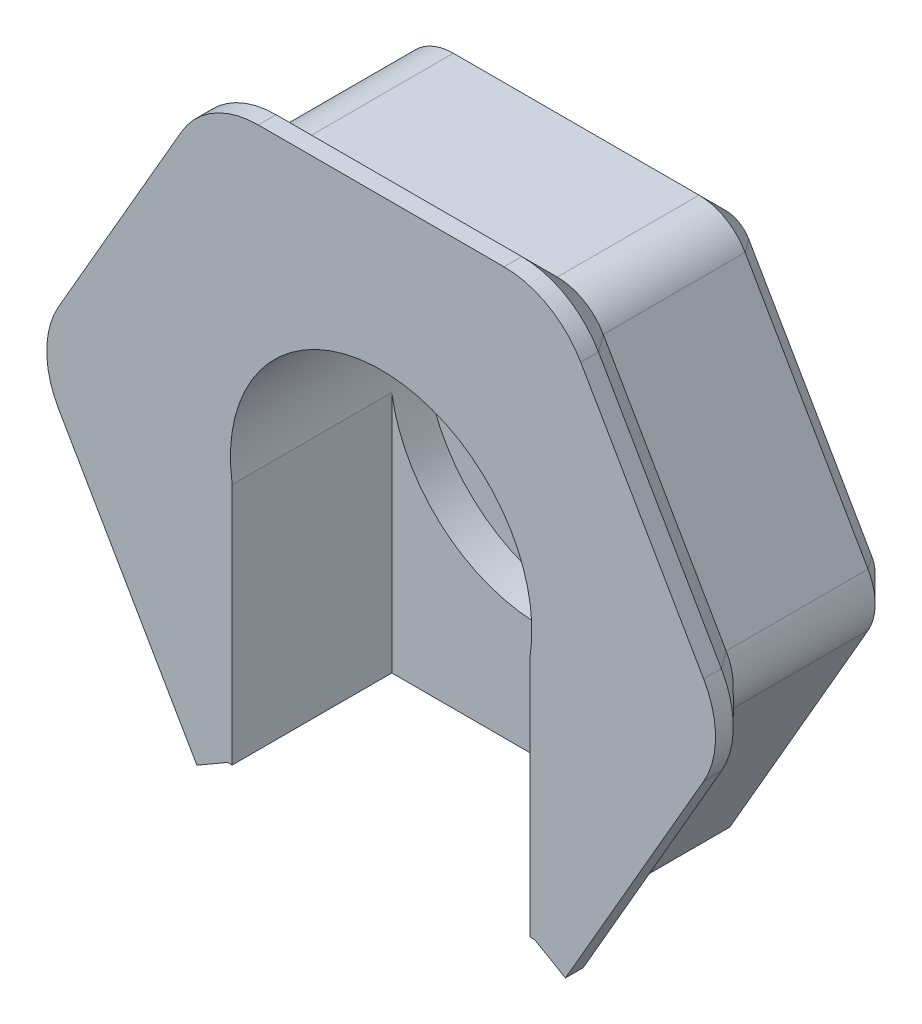
SolidWorks part; units mm, degrees
ref_plane "Front Plane" through (0, 0, 0) normal (0, 0, 1) x (1, 0, 0)
ref_plane "Top Plane" through (0, 0, 0) normal (0, 1, 0) x (1, 0, 0)
ref_plane "Right Plane" through (0, 0, 0) normal (1, 0, 0) x (0, 0, -1)
sketch "Sketch1" plane through (0, 0, 0) normal (0, 0, 1) x (1, 0, 0)
  line L1 (8.6603, 15) -> (-8.6603, 15)
  line L2 (-8.6603, 15) -> (-17.3205, 0)
  line L3 (-17.3205, 0) -> (-8.6603, -15)
  line L4 (-8.6603, -15) -> (8.6603, -15)
  line L5 (8.6603, -15) -> (17.3205, 0)
  line L6 (17.3205, 0) -> (8.6603, 15)
  circle A0 centre (0, 0) radius 15
  circle A1 centre (0, 0) radius 8.5
  circle A2 centre (0, 0) radius 15 construction
  dimension "D1" = 30
  dimension "D2" = 17
extrude "Boss-Extrude1" add sketch "Sketch1" along normal blind 1.5 contours A1 region at (0, 0, 0)
extrude "Boss-Extrude2" add sketch "Sketch1<4>" along normal offset from surface (12.5 mm away) 11 contours A0 A1 | A0 L6 L1 | A0 L1 L2 | A0 L2 L3 | A0 L5 L6 | A0 L4 L5 | A0 L3 L4 region at (7.7517, 13.4264, 0) region at (-7.7517, 13.4264, 0) region at (7.2879, 12.623, 0) region at (15.5034, 0, 0) region at (-15.5034, 0, 0) region at (-7.7517, -13.4264, 0) region at (7.7517, -13.4264, 0) up to face at (8.5, 0, 1.5) offset beyond the face yes
sketch "Sketch1<4>" plane through (0, 0, 0) normal (0, 0, 1) x (1, 0, 0) same geometry as "Sketch1"
sketch "Sketch2" plane through (0, 0, 1.5) normal (0, 0, 1) x (1, 0, 0)
  line L1 (-8.4, 0) -> (8.4, 0)
  line L2 (-8.4, 0) -> (-8.4, -15)
  line L3 (-8.4, -15) -> (8.4, -15)
  line L4 (8.4, 0) -> (8.4, -15)
  point P5 (0, 0)
  dimension "D1" = 16.8
  dimension "D2" = 15
extrude "Cut-Extrude1" cut sketch "Sketch2" along normal through all from offset 2
fillet "Fillet1" radius 3 4 edges at (-17.3205, 0, 6.25) (-8.6603, 15, 6.25) (8.6603, 15, 6.25) (17.3205, 0, 6.25)
sketch "Sketch3" plane through (0, 0, 1.5) normal (0, 0, 1) x (1, 0, 0)
  circle A0 centre (0, 0) radius 3.15
  dimension "D1" = 6.3
extrude "Cut-Extrude2" cut sketch "Sketch3" against normal through all
fillet "Fillet3" radius 1.5 10 edges at (12.5574, -8.25, 0) (16.8564, 0, 0) (12.9904, 7.5, 0) (8.4282, 14.5981, 0) (0, 15, 0) (-8.4282, 14.5981, 0) (-12.9904, 7.5, 0) (-16.8564, 0, 0) (0, -15, 0) (-12.5574, -8.25, 0) profile chamfer
sketch "Sketch5" plane through (0, 0, 12.5) normal (0, 0, 1) x (1, 0, 0)
  line L5 (-10.3923, -16) -> (-8.6603, -15)
  line L6 (10.3923, -16) -> (8.6603, -15)
  line L7 (8.6603, -15) -> (16.4545, -1.5) construction
  line L8 (16.4545, 1.5) -> (9.5263, 13.5) construction
  line L9 (6.9282, 15) -> (-6.9282, 15) construction
  line L10 (-18.1865, -2.5) -> (-10.3923, -16)
  line L11 (-11.2583, 14.5) -> (-18.1865, 2.5)
  line L12 (6.9282, 17) -> (-6.9282, 17)
  line L13 (18.1865, 2.5) -> (11.2583, 14.5)
  line L14 (10.3923, -16) -> (18.1865, -2.5)
  line L15 (-18.1865, -2.5) -> (-10.3923, -16)
  line L16 (-11.2583, 14.5) -> (-18.1865, 2.5)
  line L17 (6.9282, 17) -> (-6.9282, 17)
  line L18 (18.1865, 2.5) -> (11.2583, 14.5)
  line L19 (10.3923, -16) -> (18.1865, -2.5)
  line L20 (-9.5263, 13.5) -> (-16.4545, 1.5) construction
  line L21 (-16.4545, -1.5) -> (-8.6603, -15) construction
  line L22 (8.6603, -15) -> (16.4545, -1.5)
  line L23 (16.4545, 1.5) -> (9.5263, 13.5)
  line L24 (6.9282, 15) -> (-6.9282, 15)
  line L25 (-9.5263, 13.5) -> (-16.4545, 1.5)
  line L26 (-16.4545, -1.5) -> (-8.6603, -15)
  arc A4 (16.4545, -1.5) -> (16.4545, 1.5) centre (13.8564, 0) ccw construction
  arc A5 (9.5263, 13.5) -> (6.9282, 15) centre (6.9282, 12) ccw construction
  arc A6 (-6.9282, 15) -> (-9.5263, 13.5) centre (-6.9282, 12) ccw construction
  arc A7 (-16.4545, 1.5) -> (-16.4545, -1.5) centre (-13.8564, 0) ccw construction
  arc A8 (-18.1865, 2.5) -> (-18.1865, -2.5) centre (-13.8564, 0) ccw
  arc A9 (-6.9282, 17) -> (-11.2583, 14.5) centre (-6.9282, 12) ccw
  arc A10 (11.2583, 14.5) -> (6.9282, 17) centre (6.9282, 12) ccw
  arc A11 (18.1865, -2.5) -> (18.1865, 2.5) centre (13.8564, 0) ccw
  arc A12 (-18.1865, 2.5) -> (-18.1865, -2.5) centre (-13.8564, 0) ccw
  arc A13 (-6.9282, 17) -> (-11.2583, 14.5) centre (-6.9282, 12) ccw
  arc A14 (11.2583, 14.5) -> (6.9282, 17) centre (6.9282, 12) ccw
  arc A15 (18.1865, -2.5) -> (18.1865, 2.5) centre (13.8564, 0) ccw
  arc A16 (16.4545, -1.5) -> (16.4545, 1.5) centre (13.8564, 0) ccw
  arc A17 (9.5263, 13.5) -> (6.9282, 15) centre (6.9282, 12) ccw
  arc A18 (-6.9282, 15) -> (-9.5263, 13.5) centre (-6.9282, 12) ccw
  arc A19 (-16.4545, 1.5) -> (-16.4545, -1.5) centre (-13.8564, 0) ccw
  dimension "D1" = 2
extrude "Boss-Extrude3" add sketch "Sketch5" against normal blind 1
chamfer "Chamfer1" distance 2 angle 45 9 edges at (12.5574, -8.25, 11.5) (16.8564, 0, 11.5) (12.9904, 7.5, 11.5) (8.4282, 14.5981, 11.5) (0, 15, 11.5) (-8.4282, 14.5981, 11.5) (-12.9904, 7.5, 11.5) (-16.8564, 0, 11.5) (-12.5574, -8.25, 11.5)
